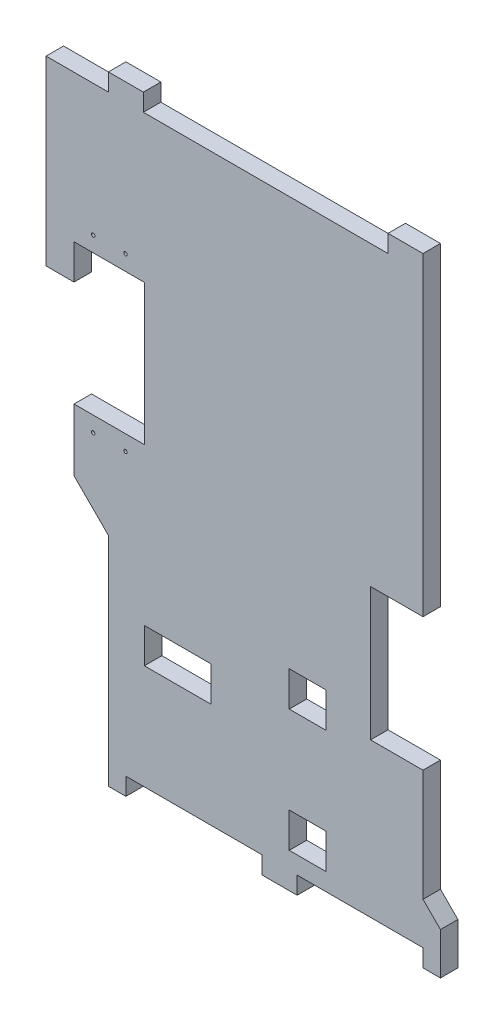
SolidWorks part; units mm, degrees
material "Balsa"
ref_plane "Plan de face" through (0, 0, 0) normal (0, 0, 1) x (1, 0, 0)
ref_plane "Plan de dessus" through (0, 0, 0) normal (0, 1, 0) x (1, 0, 0)
ref_plane "Plan de droite" through (0, 0, 0) normal (1, 0, 0) x (0, 0, -1)
sketch "Esquisse1" plane through (0, 0, 0) normal (0, 0, 1) x (1, 0, 0)
  line L0 (90, 82) -> (90, 167)
  line L1 (5, 0) -> (90, 0)
  line L2 (0, 0) -> (0, 167)
  line L3 (10, 167) -> (80, 167)
  line L4 (90, 0) -> (90, 44)
  line L5 (90, 82) -> (75, 82)
  line L6 (0, 167) -> (0, 172)
  line L7 (0, 172) -> (10, 172)
  line L8 (10, 167) -> (10, 172)
  line L9 (0, 0) -> (0, -5)
  line L10 (90, 167) -> (90, 172)
  line L11 (90, 172) -> (80, 172)
  line L12 (80, 167) -> (80, 172)
  line L13 (0, -5) -> (5, -5)
  line L14 (5, 0) -> (5, -5)
  line L16 (90, 44) -> (75, 44)
  line L17 (75, 82) -> (75, 44)
  line L18 (51.7344, 50) -> (62.2003, 50)
  line L19 (51.7344, 50) -> (51.7344, 40)
  line L20 (51.7344, 40) -> (62.2003, 40)
  line L25 (62.2003, 50) -> (62.2003, 40)
  line L32 (51.7344, 15) -> (62.2003, 15)
  line L34 (51.7344, 15) -> (51.7344, 5)
  line L35 (51.7344, 5) -> (62.2003, 5)
  line L37 (62.2003, 15) -> (62.2003, 5)
  line L54 (29.3073, 40) -> (10.2917, 40)
  line L55 (29.3073, 40) -> (29.3073, 30)
  line L56 (29.3073, 30) -> (10.2917, 30)
  line L57 (10.2917, 40) -> (10.2917, 30)
  dimension "D1" = 167
  dimension "D2" = 90
  dimension "D3" = 10
  dimension "D4" = 5
  dimension "D5" = 5
  dimension "D6" = 15
  dimension "D7" = 38
  dimension "D8" = 82
extrude "Boss.-Extru.1" add sketch "Esquisse1" along normal blind 5
sketch "Esquisse2" plane through (0, 0, 5) normal (0, 0, 1) x (1, 0, 0)
  line L0 (0, 172) -> (0, -5) construction
  line L1 (0, 167) -> (-9.8347, 167)
  line L2 (0, 167) -> (0, 57.1653)
  line L3 (0, 57.1653) -> (-9.8347, 67)
  line L4 (-9.8347, 167) -> (-9.8347, 67)
  line L6 (80, 167) -> (10, 167) construction
  dimension "D1" = 9.8347
  dimension "D2" = 135
  dimension "D3" = 100
extrude "Boss.-Extru.2" add sketch "Esquisse2" against normal blind 5
sketch "Esquisse3" plane through (0, 0, 0) normal (0, 0, -1) x (-1, 0, 0)
  line L0 (9.8347, 167) -> (9.8347, 67) construction
  line L1 (-10.3653, 125) -> (9.8347, 125)
  line L2 (-10.3653, 125) -> (-10.3653, 84.8)
  line L3 (-10.3653, 84.8) -> (9.8347, 84.8)
  line L4 (9.8347, 125) -> (9.8347, 84.8)
  line L5 (0, 167) -> (9.8347, 167) construction
  line L6 (4.3597, 129.4) -> (-4.8903, 129.4) construction
  line L7 (-4.8903, 129.4) -> (-4.8903, 80.4) construction
  line L8 (-4.8903, 80.4) -> (4.3597, 80.4) construction
  line L9 (9.8347, 167) -> (9.8347, 67) construction
  line L10 (-80, 167) -> (-10, 167) construction
  circle A0 centre (4.3597, 129.4) radius 0.5
  circle A1 centre (-4.8903, 129.4) radius 0.5
  circle A2 centre (4.3597, 80.4) radius 0.5
  circle A3 centre (-4.8903, 80.4) radius 0.5
  dimension "D9" = 1
  dimension "D1" = 17.8
  dimension "D2" = 42
  dimension "D3" = 20.2
  dimension "D4" = 9.25
  dimension "D5" = 9.25
  dimension "D6" = 49
  dimension "D7" = 14.725
  dimension "D8" = 37.6
extrude "Enlèv. mat.-Extru.1" cut sketch "Esquisse3" against normal blind 5
sketch "Esquisse4" plane through (0, 0, 5) normal (0, 0, 1) x (1, 0, 0)
  line L0 (-9.8347, 167) -> (-17.8347, 167)
  line L1 (-9.8347, 167) -> (-9.8347, 125) construction
  line L2 (-17.8347, 167) -> (-17.8347, 115)
  line L3 (-17.8347, 115) -> (-9.8347, 115)
  line L4 (-9.8347, 115) -> (-9.8347, 125)
  line L5 (-9.8347, 125) -> (-9.8347, 167)
  line L6 (0, 167) -> (-9.8347, 167) construction
  line L7 (5, 0) -> (90, 0) construction
  line L8 (44, 0) -> (54, 0)
  line L9 (44, 0) -> (44, -5)
  line L10 (44, -5) -> (54, -5)
  line L11 (54, 0) -> (54, -5)
  line L12 (0, 57.1653) -> (0, -5) construction
  line L13 (90, 0) -> (90, 44) construction
  line L14 (90, 12) -> (95, 7)
  line L15 (90, 12) -> (90, -5)
  line L16 (90, -5) -> (95, -5)
  line L17 (95, 7) -> (95, -5)
  dimension "D1" = 10
  dimension "D2" = 8
  dimension "D3" = 10
  dimension "D4" = 5
  dimension "D5" = 44
  dimension "D6" = 5
  dimension "D7" = 12
  dimension "D8" = 135
extrude "Boss.-Extru.3" add sketch "Esquisse4" against normal blind 5
